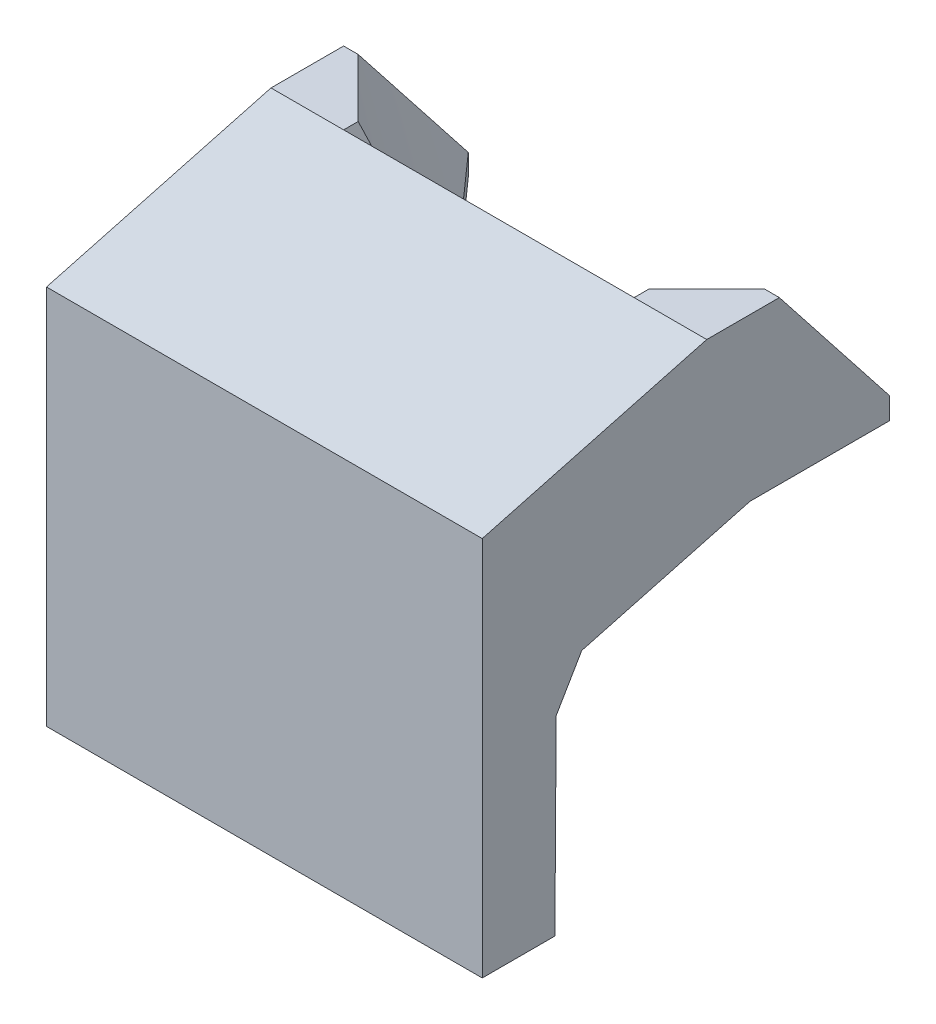
SolidWorks part; units mm, degrees
material "1060 Alloy"
ref_plane "Front Plane" through (0, 0, 0) normal (0, 0, 1) x (1, 0, 0)
ref_plane "Top Plane" through (0, 0, 0) normal (0, 1, 0) x (1, 0, 0)
ref_plane "Right Plane" through (0, 0, 0) normal (1, 0, 0) x (0, 0, -1)
sketch "Sketch1" plane through (0, 0, 0) normal (1, 0, 0) x (0, 0, -1)
  line L0 (46.9258, 408.9324) -> (341.34, 487.8205)
  line L1 (341.34, 487.8205) -> (265.5523, 770.6641)
  line L2 (265.5523, 770.6641) -> (-127, 665.48)
  line L4 (-127, 665.48) -> (-127, 0)
  line L5 (-127, 0) -> (0, 0)
  line L7 (0, 0) -> (2.2438, 332.7324)
  line L8 (2.2438, 332.7324) -> (46.9258, 408.9324)
  dimension "D1" = 665.48
  dimension "D2" = 15
  dimension "D3" = 332.74
  dimension "D4" = 304.8
  dimension "D5" = 127
  dimension "D6" = 406.4
  dimension "D7" = 150
  dimension "D8" = 76.2
extrude "Boss-Extrude1" add sketch "Sketch1" along normal blind 762
ref_plane "Plane1" through (0, 770.6641, 0) normal (0, 1, 0) x (1, 0, 0)
ref_plane "Plane2" through (0, 487.8205, 0) normal (0, 1, 0) x (1, 0, 0)
ref_plane "Plane3" through (0, 525.9205, 0) normal (0, 1, 0) x (1, 0, 0)
ref_point "Point1"
sketch "Sketch3" plane through (0, 770.6641, 0) normal (0, 1, 0) x (1, 0, 0)
  line L0 (762, 265.5523) -> (762, 392.5523)
  line L1 (762, 392.5523) -> (736.6, 392.5523)
  line L2 (736.6, 392.5523) -> (635, 290.9523)
  line L3 (635, 290.9523) -> (635, 265.5523)
  line L4 (762, 265.5523) -> (0, 265.5523) construction
  line L5 (635, 265.5523) -> (762, 265.5523)
  dimension "D4" = 127
  dimension "D3" = 127
sketch "Sketch4" plane through (0, 525.9205, 0) normal (0, 1, 0) x (1, 0, 0)
  line L0 (762, 331.1311) -> (762, 585.1311)
  line L1 (762, 585.1311) -> (736.6, 585.1311)
  line L2 (736.6, 585.1311) -> (533.4, 356.5311)
  line L3 (533.4, 356.5311) -> (533.4, 331.1311)
  line L4 (533.4, 331.1311) -> (762, 331.1311)
  line L5 (762, 341.34) -> (762, 265.5523) construction
  line L8 (762, 341.34) -> (0, 341.34) construction
  point P12 (533.4, 343.8311)
  point P16 (381, 341.34)
  dimension "D4" = 152.4
  dimension "D3" = 254
loft "Loft1" add profiles "Sketch3", "Sketch4" start constraint default connector at (762, 770.6641, -392.5523) connector at (762, 525.9205, -585.1311)
extrude "Boss-Extrude2" add sketch "Sketch4<5>" against normal blind 38.1
sketch "Sketch4<5>" plane through (0, 525.9205, 0) normal (0, 1, 0) x (1, 0, 0) same geometry as "Sketch4"
ref_plane "Plane4" through (381, 0, 0) normal (1, 0, 0) x (0, 0, -1)
mirror "Mirror1" about plane through (381, 0, 0) normal (1, 0, 0) of "Loft1", "Boss-Extrude2"
equation "\"D2@Sketch3\"=\"D1@Sketch3\""
equation "\"D2@Sketch4\"=\"D1@Sketch4\""
equation "\"D3@Sketch1\"=\"D1@Sketch1\"/2"
